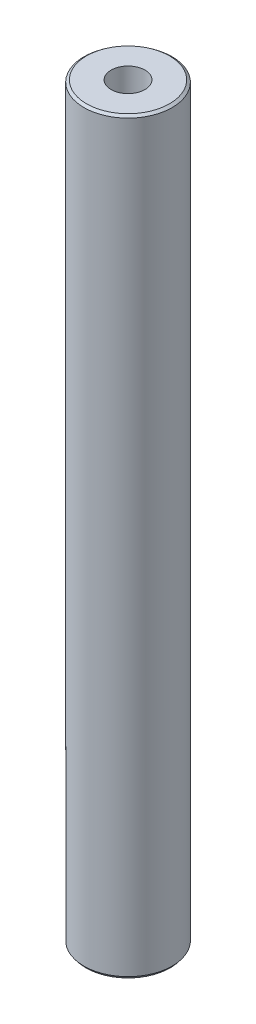
SolidWorks part; units mm, degrees
ref_plane "Front Plane" through (0, 0, 0) normal (0, 0, 1) x (1, 0, 0)
ref_plane "Top Plane" through (0, 0, 0) normal (0, 1, 0) x (1, 0, 0)
ref_plane "Right Plane" through (0, 0, 0) normal (1, 0, 0) x (0, 0, -1)
sketch "Sketch1" plane through (0, 0, 0) normal (0, 1, 0) x (1, 0, 0)
  circle A0 centre (0, 0) radius 10
  dimension "SHAFT_OD" = 20
extrude "Boss-Extrude1" add sketch "Sketch1" along normal blind 169.6297
sketch "Sketch2" plane through (0, 0, 0) normal (0, 1, 0) x (1, 0, 0)
  circle A0 centre (0, 0) radius 3.8413
  dimension "BORE_D" = 7.6825
extrude "Cut-Extrude1" cut sketch "Sketch2" along normal through all
chamfer "Chamfer1" distance 0.4532 angle 52.398 2 edges at (0, 169.6297, 10) (0, 0, 10) first distance on face at (0, 169.6297, 10) first distance on face at (0, 0, 3.8413)
